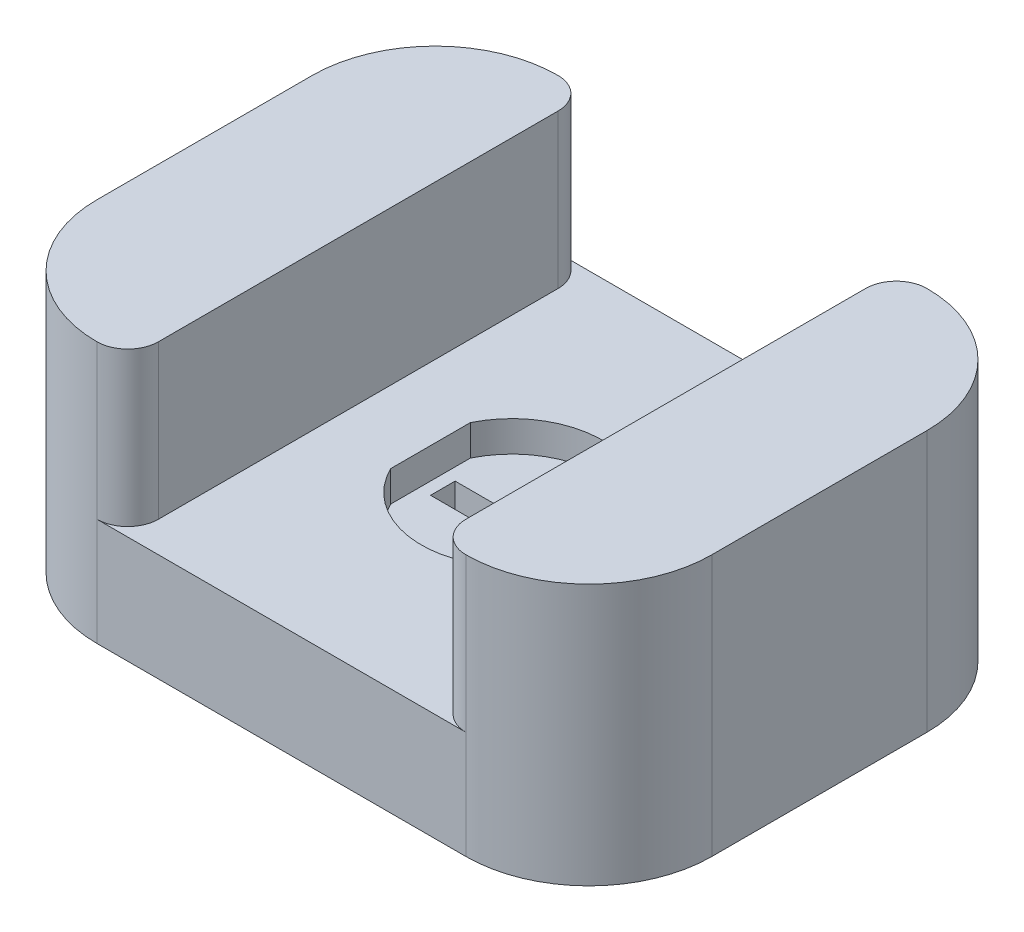
SolidWorks part; units mm, degrees
ref_plane "Front Plane" through (0, 0, 0) normal (0, 0, 1) x (1, 0, 0)
ref_plane "Top Plane" through (0, 0, 0) normal (0, 1, 0) x (1, 0, 0)
ref_plane "Right Plane" through (0, 0, 0) normal (1, 0, 0) x (0, 0, -1)
sketch "Sketch1" plane through (0, 0, 0) normal (0, 1, 0) x (1, 0, 0)
  line L1 (10, -7.5) -> (-10, -7.5)
  line L2 (10, -7.5) -> (10, 7.5)
  line L3 (10, 7.5) -> (-10, 7.5)
  line L4 (-10, -7.5) -> (-10, 7.5)
  line L5 (10, -7.5) -> (-10, 7.5) construction
  line L6 (10, 7.5) -> (-10, -7.5) construction
  point P0 (0, 0)
  dimension "D1" = 20
  dimension "D2" = 15
extrude "Boss-Extrude1" add sketch "Sketch1" along normal blind 3.5
sketch "Sketch2" plane through (0, 3.5, 0) normal (0, 1, 0) x (1, 0, 0)
  line L0 (-2.65, -1.2961) -> (-2.65, 1.2961)
  line L1 (-2.65, 0) -> (2.95, 0) construction
  arc A0 (-2.65, -1.2961) -> (-2.65, 1.2961) centre (0, 0) ccw
  dimension "D1" = 5.9
  dimension "D2" = 5.6
extrude "Cut-Extrude1" cut sketch "Sketch2" against normal blind 1
sketch "Sketch3" plane through (0, 2.5, 0) normal (0, 1, 0) x (1, 0, 0)
  line L1 (2.25, -0.4) -> (-2.25, -0.4)
  line L2 (2.25, -0.4) -> (2.25, 0.4)
  line L3 (2.25, 0.4) -> (-2.25, 0.4)
  line L4 (-2.25, -0.4) -> (-2.25, 0.4)
  line L5 (2.25, -0.4) -> (-2.25, 0.4) construction
  line L6 (2.25, 0.4) -> (-2.25, -0.4) construction
  point P0 (0, 0)
  dimension "D1" = 0.8
  dimension "D2" = 4.5
extrude "Cut-Extrude2" cut sketch "Sketch3" against normal up to next
fillet "Fillet1" radius 4 4 edges at (-10, 1.75, -7.5) (10, 1.75, -7.5) (10, 1.75, 7.5) (-10, 1.75, 7.5)
sketch "Sketch4" plane through (0, 0, 0) normal (0, -1, 0) x (1, 0, 0)
  line L0 (2.25, -0.4) -> (2.25, 0.4) construction
  line L1 (-2.25, -0.4) -> (2.25, -0.4)
  line L2 (-2.25, -0.4) -> (-2.25, -7.5)
  line L3 (-2.25, -7.5) -> (2.25, -7.5)
  line L4 (2.25, -0.4) -> (2.25, -7.5)
  line L5 (6, -7.5) -> (-6, -7.5) construction
extrude "Cut-Extrude3" cut sketch "Sketch4" against normal blind 0.4
fillet "Fillet2" radius 1 1 edges at (0, 0.4, -0.4)
sketch "Sketch5" plane through (0, 3.5, 0) normal (0, 1, 0) x (1, 0, 0)
  line L0 (-5, 7.5) -> (-5, -7.5)
  line L1 (5, 7.5) -> (5, -7.5)
  line L2 (-5, 0) -> (5, 0) construction
  line L3 (-5, 7.5) -> (-6, 7.5)
  line L4 (6, 7.5) -> (-6, 7.5)
  line L5 (-10, 3.5) -> (-10, -3.5)
  line L6 (-6, -7.5) -> (6, -7.5)
  line L7 (10, -3.5) -> (10, 3.5)
  line L8 (6, 7.5) -> (5, 7.5)
  line L9 (-10, 3.5) -> (-10, -3.5)
  line L10 (-6, -7.5) -> (-5, -7.5)
  line L11 (10, -3.5) -> (10, 3.5)
  line L12 (5, -7.5) -> (6, -7.5)
  arc A4 (-6, 7.5) -> (-10, 3.5) centre (-6, 3.5) ccw
  arc A5 (-10, -3.5) -> (-6, -7.5) centre (-6, -3.5) ccw
  arc A6 (6, -7.5) -> (10, -3.5) centre (6, -3.5) ccw
  arc A7 (10, 3.5) -> (6, 7.5) centre (6, 3.5) ccw
  arc A8 (-6, 7.5) -> (-10, 3.5) centre (-6, 3.5) ccw
  arc A9 (-10, -3.5) -> (-6, -7.5) centre (-6, -3.5) ccw
  arc A10 (6, -7.5) -> (10, -3.5) centre (6, -3.5) ccw
  arc A11 (10, 3.5) -> (6, 7.5) centre (6, 3.5) ccw
  point P18 (0, 0)
  dimension "D2" = 10
  dimension "D1" = 0
extrude "Boss-Extrude2" add sketch "Sketch5" along normal blind 5
fillet "Fillet3" radius 1 4 edges at (5, 6, -7.5) (5, 6, 7.5) (-5, 6, -7.5) (-5, 6, 7.5)
